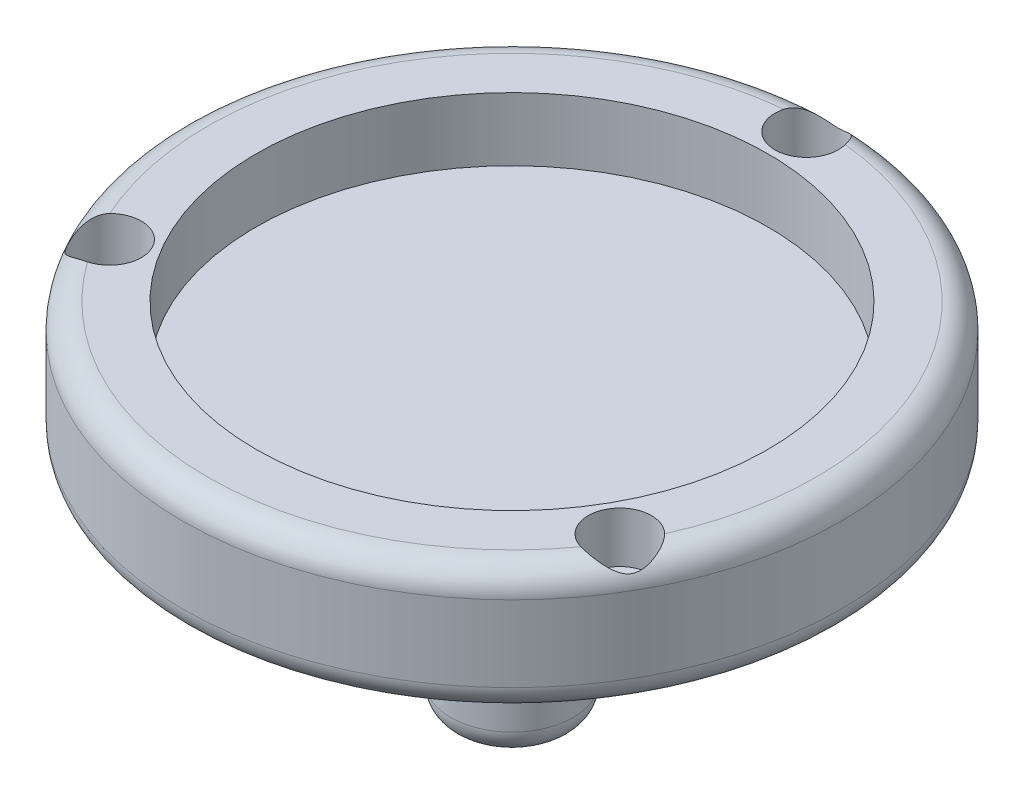
SolidWorks part; units mm, degrees
ref_plane "Front Plane" through (0, 0, 0) normal (0, 0, 1) x (1, 0, 0)
ref_plane "Top Plane" through (0, 0, 0) normal (0, 1, 0) x (1, 0, 0)
ref_plane "Right Plane" through (0, 0, 0) normal (1, 0, 0) x (0, 0, -1)
sketch "Sketch1" plane through (0, 0, 0) normal (0, 1, 0) x (1, 0, 0)
  circle A0 centre (0, 0) radius 16.51
extrude "Boss-Extrude1" add sketch "Sketch1" along normal blind 6.35
sketch "Sketch2" plane through (0, 6.35, 0) normal (0, 1, 0) x (1, 0, 0)
  circle A0 centre (0, 0) radius 12.827
extrude "Cut-Extrude1" cut sketch "Sketch2" against normal blind 3.175
sketch "Sketch3" plane through (0, 0, 0) normal (0, -1, 0) x (1, 0, 0)
  circle A0 centre (0, 0) radius 3.0734
fillet "Fillet4" radius 1.27 1 edges at (0, 6.35, 16.51)
extrude "Boss-Extrude3" add sketch "Sketch3" along normal blind 11.43 contours A0
fillet "Fillet5" radius 1.27 3 edges at (0, -11.43, -3.0734) (0, 0, 16.51) (0, 0, -3.0734)
sketch "Sketch4" plane through (0, 6.35, 0) normal (0, 1, 0) x (1, 0, 0)
  line L0 (0, 0) -> (0, 15.24) construction
  circle A0 centre (0, 0) radius 15.24 construction
  circle A1 centre (0, 0) radius 14.7571 construction
  circle A2 centre (0, 14.7571) radius 1.5875
  point P9 (0, 14.2414)
  point P10 (0, 14.7571)
extrude "Cut-Extrude2" cut sketch "Sketch4" against normal blind 2.54
ref_axis "Axis1" through (0, 3.175, 0) along (0, 1, 0)
pattern_circular "CirPattern1" count 3 over 360 about axis through (0, 3.175, 0) along (0, 1, 0) of "Cut-Extrude2" reverse direction yes
